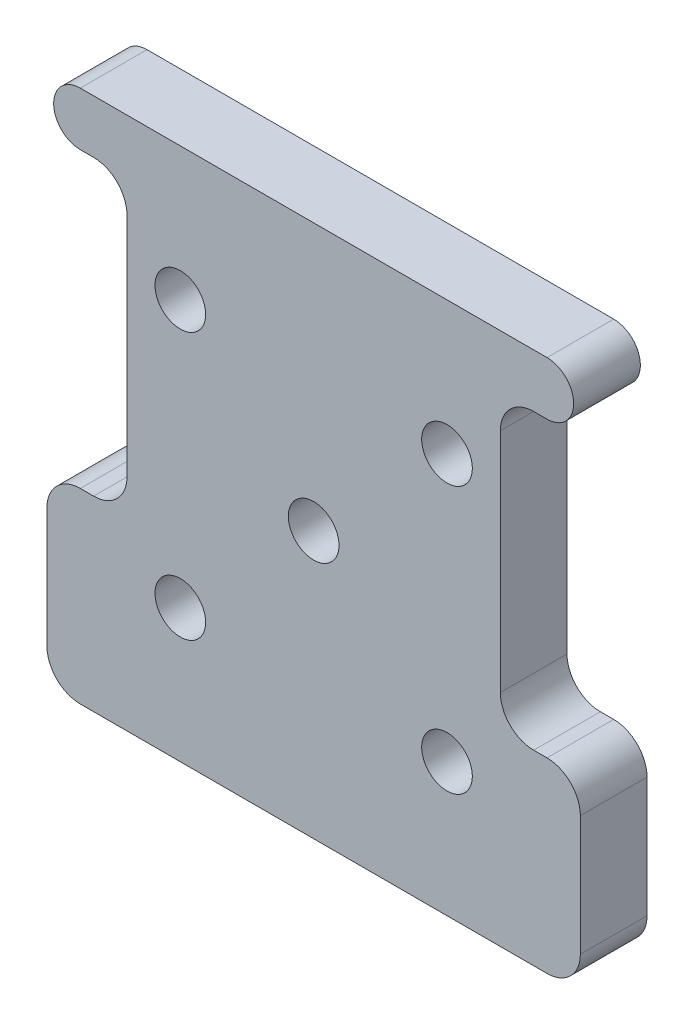
SolidWorks part; units mm, degrees
ref_plane "Front Plane" through (0, 0, 0) normal (0, 0, 1) x (1, 0, 0)
ref_plane "Top Plane" through (0, 0, 0) normal (0, 1, 0) x (1, 0, 0)
ref_plane "Right Plane" through (0, 0, 0) normal (1, 0, 0) x (0, 0, -1)
sketch "Sketch1" plane through (0, 0, 0) normal (0, 0, 1) x (1, 0, 0)
  line L0 (-25.4, 0) -> (25.4, 0)
  line L1 (25.4, 0) -> (25.4, 17.78)
  line L2 (25.4, 17.78) -> (17.78, 17.78)
  line L3 (17.78, 17.78) -> (17.78, 45.72)
  line L4 (17.78, 45.72) -> (25.4, 45.72)
  line L5 (25.4, 45.72) -> (25.4, 50.8)
  line L6 (25.4, 50.8) -> (-25.4, 50.8)
  line L7 (0, -1000) -> (0, 49000) construction
  line L8 (-25.4, 45.72) -> (-25.4, 50.8)
  line L9 (-17.78, 45.72) -> (-25.4, 45.72)
  line L10 (-17.78, 17.78) -> (-17.78, 45.72)
  line L11 (-25.4, 17.78) -> (-17.78, 17.78)
  line L12 (-25.4, 0) -> (-25.4, 17.78)
  circle A0 centre (-12.7, 12.7) radius 2.413
  circle A2 centre (12.7, 12.7) radius 2.413
  circle A3 centre (0, 25.4) radius 2.413
  circle A4 centre (-12.7, 38.1) radius 2.413
  circle A6 centre (12.7, 38.1) radius 2.413
  point P10 (0, 50.8)
  point P17 (0, 0)
  point P19 (0, 0)
  point P20 (-12.4574, 12.7)
  point P27 (13.6076, 12.7)
  point P28 (-12.7, 12.7)
  point P31 (0, 0)
  point P32 (0, 0)
  point P33 (0, 0)
  point P34 (0, 0)
  point P35 (0, 0)
  point P36 (0, 0)
  point P37 (-12.7, 38.1)
  point P38 (12.7, 38.1)
  point P39 (0, 25.4)
  dimension "D11" = 4.826
  dimension "D1" = 25.4
  dimension "D2" = 25.4
  dimension "D3" = 50.8
  dimension "D4" = 7.62
  dimension "D5" = 27.94
  dimension "D6" = 25.4
  dimension "D7" = 12.7
  dimension "D8" = 12.7
  dimension "D9" = 12.7
  dimension "D10" = 12.7
  dimension "D12" = 5.08
extrude "Boss-Extrude1" add sketch "Sketch1" along normal blind 6.35
fillet "Fillet1" radius 3.175 12 edges at (25.4, 0, 3.175) (-25.4, 0, 3.175) (-25.4, 17.78, 3.175) (-17.78, 17.78, 3.175) (-17.78, 45.72, 3.175) (-25.4, 45.72, 3.175) (25.4, 50.8, 3.175) (25.4, 45.72, 3.175) (17.78, 45.72, 3.175) (17.78, 17.78, 3.175) (25.4, 17.78, 3.175) (-25.4, 50.8, 3.175)
fillet "Fillet3" radius 2.54 2 edges at (-25.3359, 48.26, 3.175) (25.3359, 48.26, 3.175)
